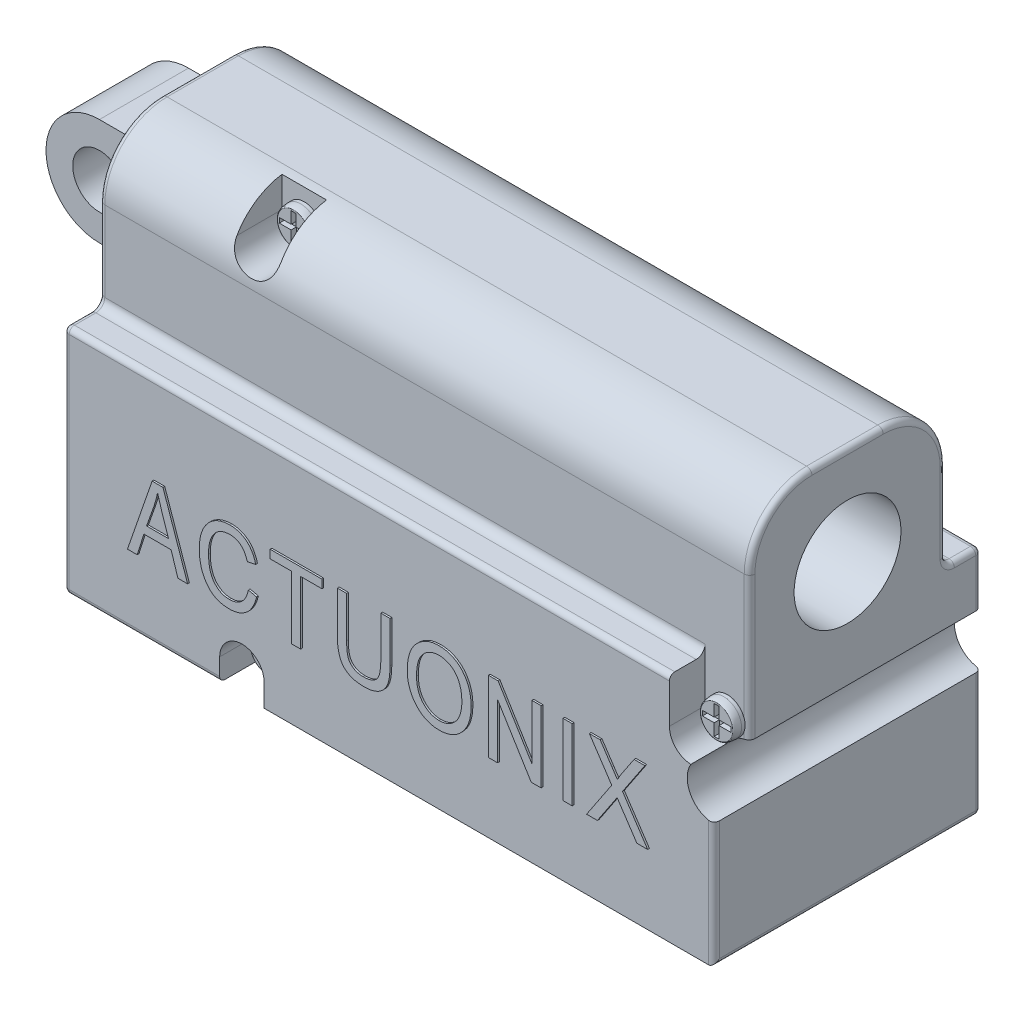
SolidWorks part; units mm, degrees
other "ConnectingWires"
other "Body"
other "Screw1"
other "Screw3"
other "Screw2"
ref_plane "Front Plane" through (0, 0, 0) normal (0, 0, 1) x (1, 0, 0)
ref_plane "Top Plane" through (0, 0, 0) normal (0, 1, 0) x (1, 0, 0)
ref_plane "Right Plane" through (0, 0, 0) normal (1, 0, 0) x (0, 0, -1)
sketch "Sketch1" plane through (0, 0, 0) normal (0, 0, 1) x (1, 0, 0)
  line L1 (-18.25, 10.75) -> (18.25, 10.75)
  line L2 (-18.25, 10.75) -> (-18.25, -10.75)
  line L3 (-18.25, -10.75) -> (18.25, -10.75)
  line L4 (18.25, 10.75) -> (18.25, -10.75)
  line L5 (-18.25, 10.75) -> (18.25, -10.75) construction
  line L6 (-18.25, -10.75) -> (18.25, 10.75) construction
  point P0 (0, 0)
  dimension "D1" = 36.5
  dimension "D2" = 21.5
extrude "Boss-Extrude1" add sketch "Sketch1" along normal mid plane 15
sketch "Sketch2" plane through (18.25, 0, 0) normal (1, 0, 0) x (0, 0, -1)
  line L0 (-7.5, -10.75) -> (-7.5, 2.25)
  line L1 (-7.5, -10.75) -> (-7.5, 10.75) construction
  line L2 (7.5, 2.25) -> (7.5, -10.75)
  line L3 (7.5, -10.75) -> (7.5, 10.75) construction
  line L4 (7.5, -10.75) -> (-7.5, -10.75)
  line L5 (0, -10.75) -> (0, 10.75) construction
  line L6 (-7.5, 10.75) -> (7.5, 10.75) construction
  line L7 (-5.5, 2.25) -> (-7.5, 2.25)
  line L8 (-5.5, 10.75) -> (5.5, 10.75)
  line L9 (-5.5, 10.75) -> (-5.5, 2.25)
  line L10 (-5.5, 2.25) -> (5.5, 2.25)
  line L11 (5.5, 10.75) -> (5.5, 2.25)
  line L12 (5.5, 2.25) -> (7.5, 2.25)
  dimension "D1" = 13
  dimension "D2" = 11
extrude "Cut-Extrude1" cut sketch "Sketch2" against normal through all contours L9 L2 L3 L7 | L11 L12 L1 L2
sketch "Sketch3" plane through (-18.25, 0, 0) normal (-1, 0, 0) x (0, 0, 1)
  line L0 (0, 10.75) -> (0, -10.75) construction
  line L1 (-2.5, 8.25) -> (2.5, 8.25)
  line L2 (-2.5, 8.25) -> (-2.5, 2.25)
  line L3 (-2.5, 2.25) -> (2.5, 2.25)
  line L4 (2.5, 8.25) -> (2.5, 2.25)
  line L5 (-2.5, 8.25) -> (2.5, 2.25) construction
  line L6 (-2.5, 2.25) -> (2.5, 8.25) construction
  line L7 (5.5, 10.75) -> (-5.5, 10.75) construction
  line L8 (7.5, -10.75) -> (-7.5, -10.75) construction
  point P0 (0, 5.25)
  point P12 (2.5, 5.25)
  dimension "D1" = 5
  dimension "D2" = 6
  dimension "D3" = 16
extrude "Boss-Extrude2" add sketch "Sketch3" along normal blind 6
sketch "Sketch4" plane through (0, 0, 2.5) normal (0, 0, 1) x (1, 0, 0)
  line L1 (-24.25, 2.25) -> (-24.25, 8.25) construction
  line L2 (-24.25, 8.25) -> (-18.25, 8.25) construction
  circle A0 centre (-21.25, 5.25) radius 1.5
  circle A1 centre (-21.25, 5.25) radius 3
  point P7 (-24.25, 5.25)
  point P9 (-21.25, 8.25)
  line M3 (-18.25, 8.25) -> (-24.25, 8.25)
  line M4 (-24.25, 8.25) -> (-24.25, 2.25)
  line M5 (-24.25, 2.25) -> (-18.25, 2.25)
  dimension "D1" = 3
extrude "Cut-Extrude2" cut sketch "Sketch4" against normal through all contours A1 M3 M4 | A1 M4 M5 | A0
sketch "Sketch5" plane through (0, 0, 7.5) normal (0, 0, 1) x (1, 0, 0)
  line L0 (18.25, -10.75) -> (18.25, 2.25) construction
  line L1 (-18.25, -10.75) -> (18.25, -10.75) construction
  circle A0 centre (18.25, -2.25) radius 1.5
  dimension "D1" = 3
  dimension "D2" = 8.5
extrude "Cut-Extrude3" cut sketch "Sketch5" against normal through all
sketch "Sketch6" plane through (18.25, 0, 0) normal (1, 0, 0) x (0, 0, -1)
  line L0 (0, 0) -> (0, 10.75) construction
  line L1 (-5.5, 10.75) -> (5.5, 10.75) construction
  line L2 (-7.5, -10.75) -> (7.5, -10.75) construction
  circle A0 centre (0, 5.25) radius 3
  point P10 (0, 8.25)
  dimension "D1" = 6
  dimension "D2" = 16
sketch "Sketch7" plane through (0, 0, 7.5) normal (0, 0, 1) x (1, 0, 0)
  line L0 (-18.25, -6.75) -> (18.25, -6.75) construction
  line L1 (-18.25, 2.25) -> (-18.25, -10.75) construction
  line L2 (18.25, -10.75) -> (18.25, -3.75) construction
  line L3 (-18.25, -10.75) -> (18.25, -10.75) construction
  text T0 "ACTUONIX" font "Arial Narrow" height 4
  dimension "D1" = 4
extrude "Lettering" add sketch "Sketch7" along normal blind 0.1
sketch "Sketch8" plane through (0, -10.75, 0) normal (0, -1, 0) x (1, 0, 0)
  line L0 (13.25, 3.5) -> (13.25, -2.75) construction
  line L1 (18.25, 7.5) -> (18.25, -7.5) construction
  line L3 (18.25, 3.5) -> (-18.25, 3.5) construction
  line L4 (-18.25, 7.5) -> (-18.25, -7.5) construction
  line L5 (-18.25, 7.5) -> (18.25, 7.5) construction
  line L6 (13.25, 7.5) -> (13.25, -7.5) construction
  line L7 (-18.25, -7.5) -> (18.25, -7.5) construction
  line L8 (14.5, 3.5) -> (14.5, -2.75)
  line L9 (12, 3.5) -> (12, -2.75)
  line L11 (13, 3.5) -> (13.5, 3.5)
  line L12 (13, 3.5) -> (13, -2.0239)
  line L13 (13, -2.0239) -> (13.5, -2.0239)
  line L14 (13.5, 3.5) -> (13.5, -2.0239)
  arc A1 (12, -2.75) -> (14.5, -2.75) centre (13.25, -2.75) ccw
  point P19 (13.25, -4)
  dimension "D1" = 4
  dimension "D2" = 5
  dimension "D3" = 7.5
  dimension "D4" = 2.5
  dimension "D5" = 0.5
  dimension "D6" = 5.5239
  dimension "D7" = 6.25
extrude "Cut-Extrude5" cut sketch "Sketch8" against normal blind 1 contours L14 L11 L12 L13
sketch "Sketch9" plane through (0, -10.75, 0) normal (0, -1, 0) x (1, 0, 0)
  line L0 (14.5, 3.5) -> (14.5, -2.75) construction
  line L1 (12, 3.5) -> (12, -2.75) construction
  line L2 (14.5, 3.5) -> (14.5, -2.75)
  line L3 (12, 3.5) -> (12, -2.75)
  line L4 (13.5, 3.5) -> (13, 3.5)
  line L5 (13.5, -2.0239) -> (13.5, 3.5)
  line L6 (13, -2.0239) -> (13.5, -2.0239)
  line L7 (13, 3.5) -> (13, -2.0239)
  line L8 (13.5, 3.5) -> (13, 3.5)
  line L9 (13.5, -2.0239) -> (13.5, 3.5)
  line L10 (13, -2.0239) -> (13.5, -2.0239)
  line L11 (13, 3.5) -> (13, -2.0239)
  line L12 (12, 3.5) -> (14.5, 3.5)
  arc A0 (12, -2.75) -> (14.5, -2.75) centre (13.25, -2.75) ccw construction
  arc A1 (12, -2.75) -> (14.5, -2.75) centre (13.25, -2.75) ccw
  line M9 (13.5, 3.5) -> (13.5, -2.0239)
  line M10 (13.5, -2.0239) -> (13, -2.0239)
  line M11 (13, -2.0239) -> (13, 3.5)
  dimension "D1" = 0
extrude "Boss-Extrude4" add sketch "Sketch9" along normal blind 0.1 contours L3 A1 L2 L12 M9 M10 M11
sketch "Sketch10" plane through (0, -9.75, 0) normal (0, -1, 0) x (1, 0, 0)
  line L0 (13, 3.5) -> (13.5, 3.5) construction
  line L1 (13.125, 3.5) -> (13.375, 3.5)
  line L2 (13.125, 3.5) -> (13.125, -2.0239)
  line L3 (13.125, -2.0239) -> (13.375, -2.0239)
  line L4 (13.375, 3.5) -> (13.375, -2.0239)
  line L5 (13, -2.0239) -> (13.5, -2.0239) construction
  line L6 (13.5, 3.5) -> (13.5, -2.0239) construction
  point P9 (13.25, 3.5)
  dimension "D1" = 0.25
  dimension "D2" = 0.25
extrude "Wires" add sketch "Sketch10" along normal blind 7 separate body
sketch "Sketch11" plane through (13.375, 0, 0) normal (1, 0, 0) x (0, 0, -1)
  line L0 (1.5221, -16.75) -> (1.5221, -9.75)
  line L1 (2.0239, -16.75) -> (-3.5, -16.75) construction
  line L2 (2.0239, -9.75) -> (-3.5, -9.75) construction
  line L3 (2.0239, -16.75) -> (2.0239, -9.75) construction
  line L4 (1.0221, -16.75) -> (1.0221, -9.75)
  line L5 (0.5221, -16.75) -> (0.5221, -9.75)
  line L6 (0.0221, -16.75) -> (0.0221, -9.75)
  line L7 (-0.4779, -16.75) -> (-0.4779, -9.75)
  line L8 (-0.9779, -16.75) -> (-0.9779, -9.75)
  line L9 (-1.4779, -16.75) -> (-1.4779, -9.75)
  line L10 (-1.9779, -16.75) -> (-1.9779, -9.75)
  line L11 (-2.4779, -16.75) -> (-2.4779, -9.75)
  line L12 (-2.9779, -16.75) -> (-2.9779, -9.75)
  line L13 (-3.5, -16.75) -> (-3.5, -9.75) construction
  line L14 (2.0239, -16.75) -> (-3.5, -16.75)
  line L15 (-3.5, -16.75) -> (-3.5, -9.75)
  line L16 (-3.5, -9.75) -> (2.0239, -9.75)
  line L17 (2.0239, -9.75) -> (2.0239, -16.75)
  line M11 (2.0239, -9.75) -> (-3.5, -9.75)
  line M13 (-3.5, -16.75) -> (2.0239, -16.75)
  dimension "D1" = 0.5018
  dimension "D3" = 0.5221
  dimension "D2" = 10
extrude "Boss-Extrude6" add sketch "Sketch11" along normal blind 0.05 contours L4 L0 M13 M11 | L6 L5 M13 M11 | L8 L7 M13 M11 | L10 L9 M13 M11 | L12 L11 M13 M11
ref_plane "Plane1" through (13.25, 0, 0) normal (1, 0, 0) x (0, 0, -1)
mirror "Mirror1" about plane through (13.25, 0, 0) normal (1, 0, 0) of "Boss-Extrude6"
sketch "Sketch12" plane through (0, 0, 7.5) normal (0, 0, 1) x (1, 0, 0)
  line L0 (17, 2.25) -> (17, -0.25) construction
  line L1 (-18.25, 2.25) -> (18.25, 2.25) construction
  line L2 (18.25, 2.25) -> (18.25, -0.25)
  line L3 (15.75, 2.25) -> (15.75, -0.25)
  line L4 (18.25, -0.75) -> (18.25, 2.25) construction
  line L5 (-18.25, 2.25) -> (18.25, 2.25) construction
  line L6 (18.25, -0.75) -> (18.25, 2.25)
  line L7 (-8.25, -10.75) -> (-8.25, -9.5) construction
  line L8 (-18.25, -10.75) -> (18.25, -10.75) construction
  line L9 (-9.5, -10.75) -> (-9.5, -9.5)
  line L10 (-7, -10.75) -> (-7, -9.5)
  line L11 (-18.25, 2.25) -> (-18.25, -10.75) construction
  arc A0 (18.25, 2.25) -> (15.75, 2.25) centre (17, 2.25) ccw
  arc A1 (15.75, -0.25) -> (18.25, -0.25) centre (17, -0.25) ccw
  arc A2 (18.25, -0.75) -> (18.25, -3.75) centre (18.25, -2.25) ccw construction
  arc A3 (18.25, -0.75) -> (16.9515, -1.4991) centre (18.25, -2.25) ccw
  arc A4 (-9.5, -10.75) -> (-7, -10.75) centre (-8.25, -10.75) ccw
  arc A5 (-7, -9.5) -> (-9.5, -9.5) centre (-8.25, -9.5) ccw
  point P4 (17, 1)
  point P20 (-8.25, -10.125)
  point P27 (-8.25, -8.25)
  dimension "D1" = 2.5
  dimension "D2" = 2.5
  dimension "D3" = 10
  dimension "D4" = 2.5
  dimension "D5" = 2.5
extrude "Cut-Extrude6" cut sketch "Sketch12" against normal up to surface (2 mm away)
sketch "Sketch13" plane through (0, 0, 5.5) normal (0, 0, 1) x (1, 0, 0)
  line L0 (-9.75, 10.75) -> (-9.75, 9) construction
  line L1 (-18.25, 10.75) -> (18.25, 10.75) construction
  line L2 (-8.5, 10.75) -> (-8.5, 9)
  line L3 (-11, 10.75) -> (-11, 9)
  line L4 (-18.25, 10.75) -> (-18.25, 2.25) construction
  arc A0 (-8.5, 10.75) -> (-11, 10.75) centre (-9.75, 10.75) ccw
  arc A1 (-11, 9) -> (-8.5, 9) centre (-9.75, 9) ccw
  point P4 (-9.75, 9.875)
  point P11 (-9.75, 7.75)
  dimension "D1" = 8.5
  dimension "D2" = 2.5
  dimension "D3" = 3
extrude "Cut-Extrude7" cut sketch "Sketch13" against normal blind 3
sketch "Sketch14" plane through (0, 0, 5.5) normal (0, 0, 1) x (1, 0, 0)
  line L0 (17, -0.25) -> (17, 10.75) construction
  line L1 (-8.5, 10.75) -> (18.25, 10.75) construction
  circle A0 centre (-8.25, -9.5) radius 1
  circle A1 centre (17, -0.0849) radius 1
  arc A2 (18.25, -0.75) -> (16.9515, -1.4991) centre (18.25, -2.25) ccw construction
  dimension "D1" = 2
extrude "Boss-Extrude7" add sketch "Sketch14" along normal blind 0.6 separate body
sketch "Sketch15" plane through (0, 0, 6.1) normal (0, 0, 1) x (1, 0, 0)
  line L1 (-9.05, -9.3625) -> (-7.45, -9.3625)
  line L3 (16.2, 0.0526) -> (17.8, 0.0526)
  line L4 (-9.05, -9.3625) -> (-9.05, -9.6375)
  line L5 (-9.05, -9.6375) -> (-7.45, -9.6375)
  line L6 (-7.45, -9.3625) -> (-7.45, -9.6375)
  line L7 (-9.05, -9.3625) -> (-7.45, -9.6375) construction
  line L8 (-9.05, -9.6375) -> (-7.45, -9.3625) construction
  line L9 (-8.3875, -8.7) -> (-8.1125, -8.7)
  line L10 (-8.3875, -8.7) -> (-8.3875, -10.3)
  line L11 (-8.3875, -10.3) -> (-8.1125, -10.3)
  line L12 (-8.1125, -8.7) -> (-8.1125, -10.3)
  line L13 (-8.3875, -8.7) -> (-8.1125, -10.3) construction
  line L14 (-8.3875, -10.3) -> (-8.1125, -8.7) construction
  line L15 (16.2, 0.0526) -> (16.2, -0.2224)
  line L16 (16.2, -0.2224) -> (17.8, -0.2224)
  line L17 (17.8, 0.0526) -> (17.8, -0.2224)
  line L18 (16.2, 0.0526) -> (17.8, -0.2224) construction
  line L19 (16.2, -0.2224) -> (17.8, 0.0526) construction
  line L20 (16.8625, -0.8849) -> (17.1375, -0.8849)
  line L21 (16.8625, -0.8849) -> (16.8625, 0.7151)
  line L22 (16.8625, 0.7151) -> (17.1375, 0.7151)
  line L23 (17.1375, -0.8849) -> (17.1375, 0.7151)
  line L24 (16.8625, -0.8849) -> (17.1375, 0.7151) construction
  line L25 (16.8625, 0.7151) -> (17.1375, -0.8849) construction
  point P0 (-8.25, -9.5)
  point P1 (-8.25, -9.5)
  point P7 (17, -0.0849)
  point P8 (17, -0.0849)
  point P14 (-8.25, -9.5)
  point P15 (17, -0.0849)
  dimension "D1" = 1.6
  dimension "D2" = 0.275
  dimension "D3" = 0.275
  dimension "D4" = 1.6
extrude "Cut-Extrude8" cut sketch "Sketch15" against normal blind 0.3 contours L16 L21 L3 L15 | L16 L23 L3 L21 | L3 L23 L22 L21 | L23 L16 L17 L3 | L20 L23 L16 L21 | L12 L5 L10 L11 | L10 L1 L4 L5 | L12 L9 L10 L1 | L1 L12 L5 L6 | L12 L1 L10 L5
sketch "Sketch16" plane through (0, 0, 2.5) normal (0, 0, 1) x (1, 0, 0)
  circle A0 centre (-9.75, 9) radius 1
  dimension "D1" = 2
extrude "Boss-Extrude8" add sketch "Sketch16" along normal blind 0.6 separate body
sketch "Sketch17" plane through (0, 0, 3.1) normal (0, 0, 1) x (1, 0, 0)
  line L1 (-9.8875, 9.8) -> (-9.6125, 9.8)
  line L2 (-9.8875, 9.8) -> (-9.8875, 8.2)
  line L3 (-9.8875, 8.2) -> (-9.6125, 8.2)
  line L4 (-9.6125, 9.8) -> (-9.6125, 8.2)
  line L5 (-9.8875, 9.8) -> (-9.6125, 8.2) construction
  line L6 (-9.8875, 8.2) -> (-9.6125, 9.8) construction
  line L7 (-10.55, 9.1375) -> (-8.95, 9.1375)
  line L8 (-10.55, 9.1375) -> (-10.55, 8.8625)
  line L9 (-10.55, 8.8625) -> (-8.95, 8.8625)
  line L10 (-8.95, 9.1375) -> (-8.95, 8.8625)
  line L11 (-10.55, 9.1375) -> (-8.95, 8.8625) construction
  line L12 (-10.55, 8.8625) -> (-8.95, 9.1375) construction
  point P0 (-9.75, 9)
  point P6 (-9.75, 9)
  dimension "D1" = 0.275
  dimension "D2" = 1.6
extrude "Cut-Extrude9" cut sketch "Sketch17" against normal blind 0.3 contours L9 L2 L3 L4 | L10 L7 L4 L9 | L2 L9 L4 L7 | L8 L9 L2 L7 | L2 L7 L4 L1
fillet "Fillet6" radius 0.1 1 edges at (-8.75, 9, 3.1)
fillet "Fillet7" radius 0.1 1 edges at (-7.25, -9.5, 6.1)
fillet "Fillet8" radius 0.1 1 edges at (18, -0.0849, 6.1)
fillet "Fillet1" radius 3.5 3 edges at (0, 10.75, -5.5) (4.875, 10.75, 5.5) (-14.625, 10.75, 5.5)
fillet "Fillet2" radius 1 2 edges at (-18.25, 2.25, 0) (-18.25, 8.25, 0)
fillet "Fillet3" radius 0.5 2 edges at (-18.25, 5.25, 2.5) (-18.25, 5.25, -2.5)
fillet "Fillet4" radius 0.5 2 edges at (-1.25, 2.25, 5.5) (0, 2.25, -5.5)
fillet "Fillet5" radius 0.3 26 edges at (-18.25, -4.25, -7.5) (-18.25, -4.25, 7.5) (-1.25, 2.25, 7.5) (0, 2.25, -7.5) (18.25, -7.25, 7.5) (18.25, 5, -5.5) (-18.25, 5, -5.5) (18.25, 3.25, 5.5) (18.25, 10.75, 0) (18.25, 9.7249, 4.4749) (18.25, 9.7249, -4.4749) (-18.25, 10.75, 0) (-18.25, 5, 5.5) (-18.25, 9.7249, 4.4749) (-18.25, 9.7249, -4.4749) (0, -10.75, -7.5) (-18.25, 2.25, 6.75) (18.25, 2.25, -6.75) (-18.25, 2.25, -6.75) (-18.25, 2.3964, 5.6464) (18.25, 2.3964, -5.6464) (-18.25, 2.3964, -5.6464) (18.25, -7.25, -7.5) (18.25, -10.75, 0) (-18.25, -10.75, 0) (18.25, 0.75, -7.5)
extrude "Cut-Extrude4" cut sketch "Sketch6" against normal blind 25
sketch "Sketch18" plane through (0, 0, -7.5) normal (0, 0, -1) x (-1, 0, 0)
  line L1 (-19.3487, -11.2713) -> (-8.0609, -11.2713)
  line L2 (-19.3487, -11.2713) -> (-19.3487, -20.1558)
  line L3 (-19.3487, -20.1558) -> (-8.0609, -20.1558)
  line L4 (-8.0609, -11.2713) -> (-8.0609, -20.1558)
  line L5 (-19.3487, -11.2713) -> (-8.0609, -20.1558) construction
  line L6 (-19.3487, -20.1558) -> (-8.0609, -11.2713) construction
  point P0 (-13.7048, -15.7135)
extrude "Cut-Extrude10" cut sketch "Sketch18" against normal through all
